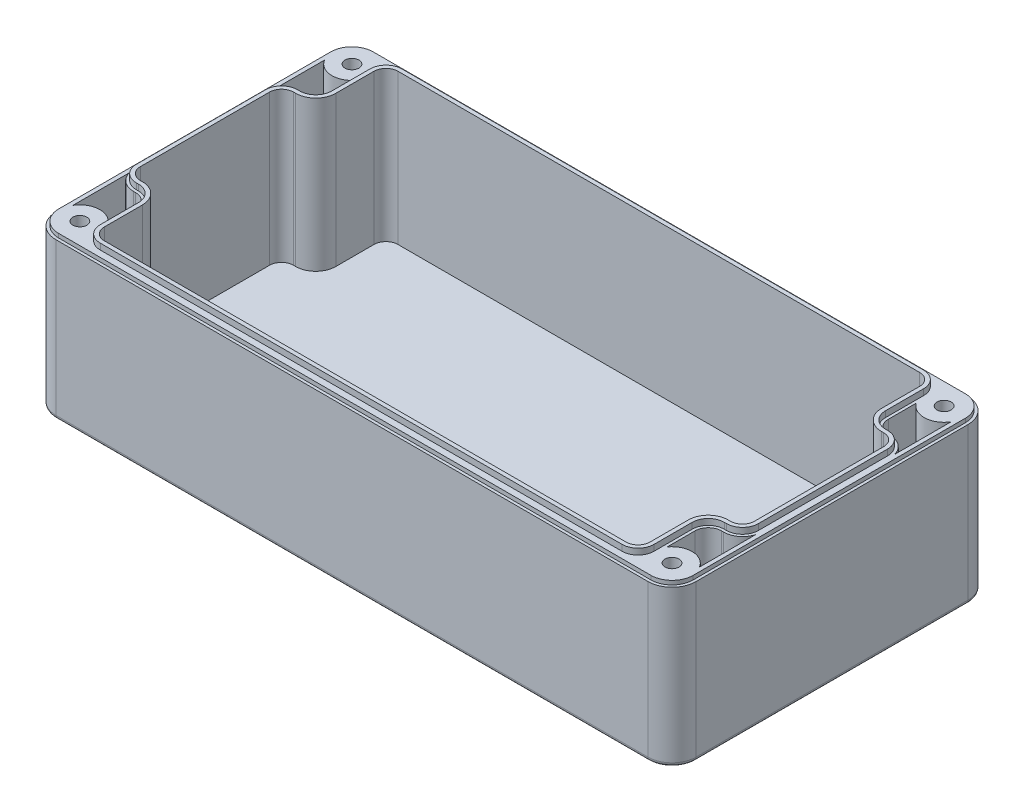
SolidWorks part; units mm, degrees
ref_plane "Спереди" through (0, 0, 0) normal (0, 0, 1) x (1, 0, 0)
ref_plane "Сверху" through (0, 0, 0) normal (0, 1, 0) x (1, 0, 0)
ref_plane "Справа" through (0, 0, 0) normal (1, 0, 0) x (0, 0, -1)
sketch "Эскиз1" plane through (0, 0, 0) normal (0, 1, 0) x (1, 0, 0)
  line L1 (-74, 40) -> (74, 40)
  line L2 (-80, 34) -> (-80, -34)
  line L3 (-74, -40) -> (74, -40)
  line L4 (80, 34) -> (80, -34)
  line L5 (-80, 40) -> (80, -40) construction
  line L6 (-80, -40) -> (80, 40) construction
  arc A0 (74, 40) -> (80, 34) centre (74, 34) cw
  arc A1 (80, -34) -> (74, -40) centre (74, -34) cw
  arc A2 (-74, -40) -> (-80, -34) centre (-74, -34) cw
  arc A3 (-80, 34) -> (-74, 40) centre (-74, 34) cw
  point P0 (0, 0)
  dimension "D3" = 6
  dimension "D1" = 160
  dimension "D2" = 80
extrude "Бобышка-Вытянуть1" add sketch "Эскиз1" along normal blind 40
sketch "Эскиз2" plane through (0, 0, 0) normal (0, 1, 0) x (1, 0, 0)
  line L0 (-68.2, 33.7) -> (-68.2, 24.15)
  line L1 (-73.2, 19.15) -> (-73.75, 19.15)
  line L2 (-76.75, 16.15) -> (-76.75, -16.15)
  line L3 (-73.75, -19.15) -> (-73.2, -19.15)
  line L4 (-68.2, -24.15) -> (-68.2, -33.7)
  line L5 (-65.2, -36.7) -> (65.2, -36.7)
  line L6 (68.2, -33.7) -> (68.2, -24.15)
  line L7 (73.2, -19.15) -> (73.75, -19.15)
  line L8 (76.75, -16.15) -> (76.75, 16.15)
  line L9 (73.75, 19.15) -> (73.2, 19.15)
  line L10 (68.2, 24.15) -> (68.2, 33.7)
  line L11 (65.2, 36.7) -> (-65.2, 36.7)
  line L12 (-76.75, 0) -> (76.75, 0) construction
  line L13 (0, 36.7) -> (0, -36.7) construction
  arc A0 (68.2, 24.15) -> (73.2, 19.15) centre (73.2, 24.15) ccw
  arc A1 (73.2, -19.15) -> (68.2, -24.15) centre (73.2, -24.15) ccw
  arc A2 (-68.2, -24.15) -> (-73.2, -19.15) centre (-73.2, -24.15) ccw
  arc A3 (-73.2, 19.15) -> (-68.2, 24.15) centre (-73.2, 24.15) ccw
  arc A4 (65.2, 36.7) -> (68.2, 33.7) centre (65.2, 33.7) cw
  arc A5 (73.75, 19.15) -> (76.75, 16.15) centre (73.75, 16.15) cw
  arc A6 (76.75, -16.15) -> (73.75, -19.15) centre (73.75, -16.15) cw
  arc A7 (68.2, -33.7) -> (65.2, -36.7) centre (65.2, -33.7) cw
  arc A8 (-65.2, -36.7) -> (-68.2, -33.7) centre (-65.2, -33.7) cw
  arc A9 (-73.75, -19.15) -> (-76.75, -16.15) centre (-73.75, -16.15) cw
  arc A10 (-76.75, 16.15) -> (-73.75, 19.15) centre (-73.75, 16.15) cw
  arc A11 (-68.2, 33.7) -> (-65.2, 36.7) centre (-65.2, 33.7) cw
  dimension "D4" = 153.5
  dimension "D1" = 5
  dimension "D2" = 3
  dimension "D3" = 73.4
  dimension "D5" = 38.3
  dimension "D6" = 136.4
extrude "Вырез-Вытянуть1" cut sketch "Эскиз2" along normal up to surface (40 mm away) from offset 4 up to face at (0, 40, 0)
sketch "Эскиз3" plane through (0, 0, 0) normal (0, 1, 0) x (1, 0, 0)
  line L8 (-78.3, 34) -> (-78.3, -34)
  line L9 (-74, -38.3) -> (74, -38.3)
  line L10 (78.3, -34) -> (78.3, 34)
  line L11 (74, 38.3) -> (-74, 38.3)
  line L12 (-78.3, 34) -> (-78.3, -34)
  line L13 (-74, -38.3) -> (74, -38.3)
  line L14 (78.3, -34) -> (78.3, 34)
  line L15 (74, 38.3) -> (-74, 38.3)
  line L36 (69.9, 24.15) -> (69.9, 33.7)
  line L37 (73.75, 20.85) -> (73.2, 20.85)
  line L38 (78.45, -16.15) -> (78.45, 16.15)
  line L39 (73.2, -20.85) -> (73.75, -20.85)
  line L40 (69.9, -33.7) -> (69.9, -24.15)
  line L41 (-65.2, -38.4) -> (65.2, -38.4)
  line L42 (-69.9, -24.15) -> (-69.9, -33.7)
  line L43 (-73.75, -20.85) -> (-73.2, -20.85)
  line L44 (-78.45, 16.15) -> (-78.45, -16.15)
  line L45 (-73.2, 20.85) -> (-73.75, 20.85)
  line L46 (-69.9, 33.7) -> (-69.9, 24.15)
  line L47 (65.2, 38.4) -> (-65.2, 38.4)
  line L48 (69.9, 24.15) -> (69.9, 33.7)
  line L49 (73.75, 20.85) -> (73.2, 20.85)
  line L50 (78.45, -16.15) -> (78.45, 16.15)
  line L51 (73.2, -20.85) -> (73.75, -20.85)
  line L52 (69.9, -33.7) -> (69.9, -24.15)
  line L53 (-65.2, -38.4) -> (65.2, -38.4)
  line L54 (-69.9, -24.15) -> (-69.9, -33.7)
  line L55 (-73.75, -20.85) -> (-73.2, -20.85)
  line L56 (-78.45, 16.15) -> (-78.45, -16.15)
  line L57 (-73.2, 20.85) -> (-73.75, 20.85)
  line L58 (-69.9, 33.7) -> (-69.9, 24.15)
  line L59 (65.2, 38.4) -> (-65.2, 38.4)
  circle A0 centre (-74, 34) radius 5
  arc A8 (-74, 38.3) -> (-78.3, 34) centre (-74, 34) ccw
  arc A9 (-78.3, -34) -> (-74, -38.3) centre (-74, -34) ccw
  arc A10 (74, -38.3) -> (78.3, -34) centre (74, -34) ccw
  arc A11 (78.3, 34) -> (74, 38.3) centre (74, 34) ccw
  arc A12 (-74, 38.3) -> (-78.3, 34) centre (-74, 34) ccw
  arc A13 (-78.3, -34) -> (-74, -38.3) centre (-74, -34) ccw
  arc A14 (74, -38.3) -> (78.3, -34) centre (74, -34) ccw
  arc A15 (78.3, 34) -> (74, 38.3) centre (74, 34) ccw
  arc A36 (69.9, 33.7) -> (65.2, 38.4) centre (65.2, 33.7) ccw
  arc A37 (69.9, 24.15) -> (73.2, 20.85) centre (73.2, 24.15) ccw
  arc A38 (78.45, 16.15) -> (73.75, 20.85) centre (73.75, 16.15) ccw
  arc A39 (73.75, -20.85) -> (78.45, -16.15) centre (73.75, -16.15) ccw
  arc A40 (73.2, -20.85) -> (69.9, -24.15) centre (73.2, -24.15) ccw
  arc A41 (65.2, -38.4) -> (69.9, -33.7) centre (65.2, -33.7) ccw
  arc A42 (-69.9, -33.7) -> (-65.2, -38.4) centre (-65.2, -33.7) ccw
  arc A43 (-69.9, -24.15) -> (-73.2, -20.85) centre (-73.2, -24.15) ccw
  arc A44 (-78.45, -16.15) -> (-73.75, -20.85) centre (-73.75, -16.15) ccw
  arc A45 (-73.75, 20.85) -> (-78.45, 16.15) centre (-73.75, 16.15) ccw
  arc A46 (-73.2, 20.85) -> (-69.9, 24.15) centre (-73.2, 24.15) ccw
  arc A47 (-65.2, 38.4) -> (-69.9, 33.7) centre (-65.2, 33.7) ccw
  arc A48 (69.9, 33.7) -> (65.2, 38.4) centre (65.2, 33.7) ccw
  arc A49 (69.9, 24.15) -> (73.2, 20.85) centre (73.2, 24.15) ccw
  arc A50 (78.45, 16.15) -> (73.75, 20.85) centre (73.75, 16.15) ccw
  arc A51 (73.75, -20.85) -> (78.45, -16.15) centre (73.75, -16.15) ccw
  arc A52 (73.2, -20.85) -> (69.9, -24.15) centre (73.2, -24.15) ccw
  arc A53 (65.2, -38.4) -> (69.9, -33.7) centre (65.2, -33.7) ccw
  arc A54 (-69.9, -33.7) -> (-65.2, -38.4) centre (-65.2, -33.7) ccw
  arc A55 (-69.9, -24.15) -> (-73.2, -20.85) centre (-73.2, -24.15) ccw
  arc A56 (-78.45, -16.15) -> (-73.75, -20.85) centre (-73.75, -16.15) ccw
  arc A57 (-73.75, 20.85) -> (-78.45, 16.15) centre (-73.75, 16.15) ccw
  arc A58 (-73.2, 20.85) -> (-69.9, 24.15) centre (-73.2, 24.15) ccw
  arc A59 (-65.2, 38.4) -> (-69.9, 33.7) centre (-65.2, 33.7) ccw
  dimension "D3" = 10
  dimension "D1" = 1.7
  dimension "D2" = 1.7
extrude "Вырез-Вытянуть2" cut sketch "Эскиз3" along normal up to surface (40 mm away) from offset 2.5 contours L57 A58 L58 A0 L12 A57 region at (-74.3973, 0, -25.1085) up to face at (0, 40, 0)
mirror "Зеркальное отражение1" about plane through (0, 0, 0) normal (0, 0, 1) of "Вырез-Вытянуть2"
mirror "Зеркальное отражение2" about plane through (0, 0, 0) normal (1, 0, 0) of "Зеркальное отражение1"
extrude "Вытянуть-Тонкостенный1" add sketch "Эскиз2<2>" along normal blind 1.5 from surface thin contours L11 A11 L0 A3 L1 A10 L2 A9 L3 A2 L4 A8 L5 A7 L6 A1 L7 A6 L8 A5 L9 A0 L10 A4 starting at face at (-73.8922, 40, 23.9281) thin type one direction wall 1
sketch "Эскиз2<2>" plane through (0, 0, 0) normal (0, 1, 0) x (1, 0, 0) same geometry as "Эскиз2"
sketch "Эскиз6" plane through (0, 0, 0) normal (0, 1, 0) x (1, 0, 0)
  circle A0 centre (-74, 34) radius 3.75
  circle A1 centre (-74, -34) radius 3.75
  circle A2 centre (74, -34) radius 3.75
  circle A3 centre (74, 34) radius 3.75
  dimension "D1" = 7.5
extrude "Вырез-Вытянуть3" cut sketch "Эскиз6" along normal blind 32
sketch "Эскиз7" plane through (0, 0, 0) normal (0, 1, 0) x (1, 0, 0)
  circle A0 centre (-74, 34) radius 1.75
  circle A1 centre (-74, -34) radius 1.75
  circle A2 centre (74, -34) radius 1.75
  circle A3 centre (74, 34) radius 1.75
  dimension "D1" = 3.5
extrude "Вырез-Вытянуть4" cut sketch "Эскиз7" along normal up to surface (40 mm away) up to face at (0, 40, 0)
fillet "Скругление1" radius 1 8 edges at (78.2426, 0, -38.2426) (80, 0, 0) (78.2426, 0, 38.2426) (0, 0, 40) (-78.2426, 0, 38.2426) (-80, 0, 0) (-78.2426, 0, -38.2426) (0, 0, -40)
sketch "Эскиз8" plane through (0, 0, 0) normal (0, 1, 0) x (1, 0, 0)
  line L1 (-74.15, 25.1) -> (74.15, 25.1) construction
  line L2 (-74.15, 25.1) -> (-74.15, -25.1) construction
  line L3 (-74.15, -25.1) -> (74.15, -25.1) construction
  line L4 (74.15, 25.1) -> (74.15, -25.1) construction
  line L5 (-74.15, 25.1) -> (74.15, -25.1) construction
  line L6 (-74.15, -25.1) -> (74.15, 25.1) construction
  circle A0 centre (-74.15, 25.1) radius 2.1
  circle A1 centre (-74.15, -25.1) radius 2.1
  circle A2 centre (74.15, -25.1) radius 2.1
  circle A3 centre (74.15, 25.1) radius 2.1
  point P0 (0, 0)
  dimension "D3" = 4.2
  dimension "D1" = 50.2
  dimension "D2" = 148.3
extrude "Вырез-Вытянуть5" cut sketch "Эскиз8" along normal up to surface (2.5 mm away) up to face at (-73.8922, 2.5, -23.9281)
extrude "Вырез-Вытянуть-Тонкостенный1" cut sketch "Эскиз1<2>" against normal blind 1 from surface thin starting at face at (74, 40, 32.25) thin type one direction reverse wall 0.7
sketch "Эскиз1<2>" plane through (0, 0, 0) normal (0, 1, 0) x (1, 0, 0) same geometry as "Эскиз1"
